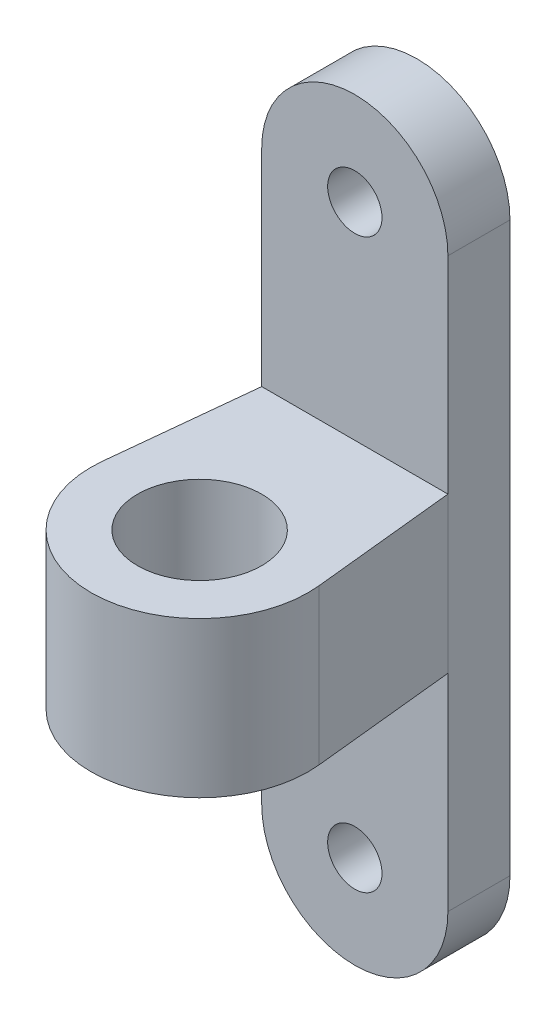
SolidWorks part; units mm, degrees
ref_plane "Plano frontal" through (0, 0, 0) normal (0, 0, 1) x (1, 0, 0)
ref_plane "Plano superior" through (0, 0, 0) normal (0, 1, 0) x (1, 0, 0)
ref_plane "Plano direito" through (0, 0, 0) normal (1, 0, 0) x (0, 0, -1)
sketch "Esboço1" plane through (0, 0, 0) normal (0, 0, 1) x (1, 0, 0)
  line L0 (0, 0) -> (0, 36.6) construction
  line L1 (-6, 0) -> (-6, 36.6)
  line L2 (6, 0) -> (6, 36.6)
  circle A0 centre (0, 0) radius 1.75
  circle A1 centre (0, 36.6) radius 1.75
  arc A2 (-6, 0) -> (6, 0) centre (0, 0) ccw
  arc A3 (6, 36.6) -> (-6, 36.6) centre (0, 36.6) ccw
  point P5 (0, 18.3)
  dimension "D1" = 36.6
  dimension "D2" = 3.5
  dimension "D3" = 6
extrude "Ressalto-extrusão1" add sketch "Esboço1" along normal blind 4
sketch "Esboço2" plane through (0, 0, 0) normal (0, 0, -1) x (-1, 0, 0)
  line L0 (0, 36.6) -> (0, 0) construction
  line L2 (16.4836, 23.3) -> (-16.4836, 23.3)
  line L3 (16.4836, 23.3) -> (16.4836, 13.3)
  line L4 (16.4836, 13.3) -> (-16.4836, 13.3)
  line L5 (-16.4836, 23.3) -> (-16.4836, 13.3)
  line L6 (16.4836, 23.3) -> (-16.4836, 13.3) construction
  line L7 (16.4836, 13.3) -> (-16.4836, 23.3) construction
  point P4 (0, 18.3)
  dimension "D1" = 10
extrude "Ressalto-extrusão2" add sketch "Esboço2" against normal blind 25
sketch "Esboço3" plane through (0, 23.3, 0) normal (0, 1, 0) x (1, 0, 0)
  line L0 (-6, -4) -> (-6.9626, -13.2776)
  line L3 (0, 0) -> (0, -17.438) construction
  line L4 (-6, -4) -> (-6, 0)
  line L5 (6, -4) -> (-6, -4) construction
  line L6 (6, -4) -> (6.9626, -13.2776)
  line L7 (-6, 0) -> (-6, -4) construction
  line L8 (-16.4836, 0) -> (-6, 0) construction
  line L9 (-6, 0) -> (6, 0)
  line L10 (6, 0) -> (6, -4)
  circle A0 centre (0, -14) radius 4
  arc A1 (-6.9626, -13.2776) -> (6.9626, -13.2776) centre (0, -14) ccw
  point P7 (0, -4)
  line M4 (6, 0) -> (6, -4)
  line M6 (-6, -4) -> (-6, 0)
  line M7 (-6, 0) -> (-16.4836, 0)
  line M8 (-16.4836, 0) -> (-16.4836, -25)
  line M9 (-16.4836, -25) -> (16.4836, -25)
  line M10 (16.4836, -25) -> (16.4836, 0)
  line M11 (16.4836, 0) -> (6, 0)
  dimension "D1" = 4
  dimension "D3" = 7
extrude "Corte-extrusão3" cut sketch "Esboço3" against normal through all contours A1 L0 M6 M7 M8 M9 | A1 L6 M9 M10 M11 M4 | A0 M9 region at (-6.8928, 23.3, 8.5961) region at (0, 23.3, 14)
